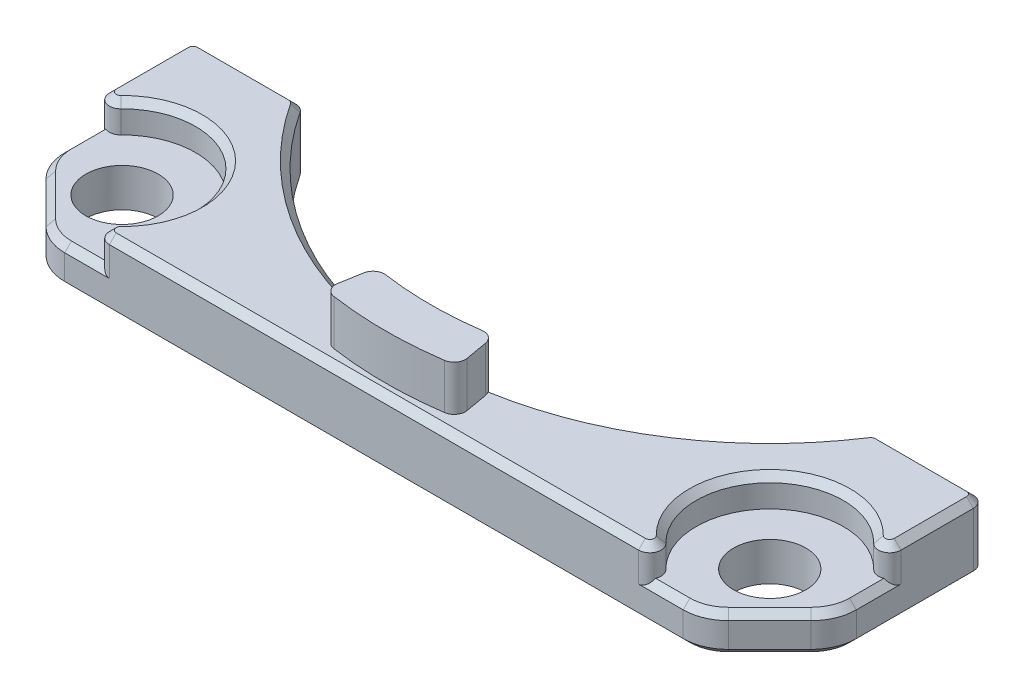
SolidWorks part; units mm, degrees
material "6061 合金"
ref_plane "前视基准面" through (0, 0, 0) normal (0, 0, 1) x (1, 0, 0)
ref_plane "上视基准面" through (0, 0, 0) normal (0, 1, 0) x (1, 0, 0)
ref_plane "右视基准面" through (0, 0, 0) normal (1, 0, 0) x (0, 0, -1)
other "Configuration Table"
sketch "草图1" plane through (0, 0, 0) normal (0, 1, 0) x (1, 0, 0)
  line L0 (-12.6886, -8) -> (-17.5, -8)
  line L1 (-17.5, 17.5) -> (17.5, 17.5) construction
  line L2 (-17.5, 17.5) -> (-17.5, -17.5) construction
  line L3 (-17.5, -17.5) -> (17.5, -17.5) construction
  line L4 (17.5, 17.5) -> (17.5, -17.5) construction
  line L5 (-17.5, 17.5) -> (17.5, -17.5) construction
  line L6 (-17.5, -17.5) -> (17.5, 17.5) construction
  line L7 (12.6886, -8) -> (17.5, -8)
  line L8 (-17.5, -8) -> (-17.5, -17.5)
  line L9 (-17.5, -17.5) -> (17.5, -17.5)
  line L10 (17.5, -17.5) -> (17.5, -8)
  arc A0 (-12.6886, -8) -> (12.6886, -8) centre (0, 0) ccw
  point P0 (0, 0)
  dimension "D3" = 30
  dimension "D1" = 35
  dimension "D2" = 35
  dimension "D4" = 8
extrude "凸台-拉伸1" add sketch "草图1" along normal blind 3
chamfer "倒角1" distance 3 angle 45 2 edges at (-17.5, 1.5, 17.5) (17.5, 1.5, 17.5)
sketch "草图2" plane through (0, 3, 0) normal (0, 1, 0) x (1, 0, 0)
  line L0 (0, 0) -> (14.3189, -14.3189) construction
  line L1 (0, 0) -> (0, -20.25) construction
  circle A0 centre (0, 0) radius 20.25 construction
  circle A1 centre (14.3189, -14.3189) radius 1.6
  circle A2 centre (-14.3189, -14.3189) radius 1.6
  dimension "D1" = 40.5
  dimension "D3" = 3.2
  dimension "D2" = 45
extrude "切除-拉伸1" cut sketch "草图2" against normal blind 3
sketch "草图3" plane through (0, 3, 0) normal (0, 1, 0) x (1, 0, 0)
  line L0 (-2.6047, -14.7721) -> (-2.952, -16.7417)
  line L1 (-14.5, -17.5) -> (14.5, -17.5) construction
  line L2 (0, 0) -> (0, -17.5) construction
  line L6 (2.6047, -14.7721) -> (2.952, -16.7417)
  arc A0 (-12.6886, -8) -> (12.6886, -8) centre (0, 0) ccw construction
  arc A1 (-2.6047, -14.7721) -> (2.6047, -14.7721) centre (0, 0) ccw
  arc A3 (-2.6047, -14.7721) -> (2.6047, -14.7721) centre (0, 0) ccw
  arc A4 (-2.952, -16.7417) -> (2.952, -16.7417) centre (0, 0) ccw
  arc M12 (12.6886, -8) -> (-12.6886, -8) centre (0, 0) cw
  dimension "D2" = 34
  dimension "D1" = 10
  dimension "D3" = 10
extrude "凸台-拉伸2" add sketch "草图3" along normal blind 2 contours L2 A3 L0 A4 | L2 A4 L6 M12 region at (-1.3945, 3, 15.9396) region at (1.3945, 3, 15.9396)
sketch "草图5" plane through (0, 3, 0) normal (0, 1, 0) x (1, 0, 0)
  circle A0 centre (-14.3189, -14.3189) radius 3.25
  circle A1 centre (14.3189, -14.3189) radius 3.25
  dimension "D1" = 6.5
  dimension "D2" = 6.5
extrude "切除-拉伸2" cut sketch "草图5" against normal blind 1.3
fillet "圆角1" radius 0.5 8 edges at (12.6886, 1.5, 8) (-12.6886, 1.5, 8) (-17.5, 1.5, 8) (17.5, 1.5, 8) (17.5, 2.35, 13.6532) (13.6532, 2.35, 17.5) (-13.6532, 2.35, 17.5) (-17.5, 2.35, 13.6532)
fillet "圆角5" radius 0.5 4 edges at (-2.6047, 4, 14.7721) (2.6047, 4, 14.7721) (2.952, 4, 16.7417) (-2.952, 4, 16.7417)
fillet "圆角4" radius 2 4 edges at (17.5, 0.85, 14.5) (14.5, 0.85, 17.5) (-14.5, 0.85, 17.5) (-17.5, 0.85, 14.5)
chamfer "倒角2" distance 0.3 angle 45 33 edges at (-17.5, 3, 10.0985) (-17.1888, 3, 12.16) (-17.3536, 3, 8.1464) (-12.0208, 3, 12.0208) (-14.9807, 3, 8) (-12.16, 3, 17.1888) (-12.7239, 3, 8.0601) (-8.0479, 3, 12.6583) (12.16, 3, 17.1888) (12.0208, 3, 12.0208) (17.1888, 3, 12.16) (17.5, 3, 10.0985) (17.3536, 3, 8.1464) (14.9807, 3, 8) (12.7239, 3, 8.0601) (8.0479, 3, 12.6583) (17.3536, 0, 8.1464) (14.9807, 0, 8) (12.7239, 0, 8.0601) (0, 0, 15) (-12.7239, 0, 8.0601) (-14.9807, 0, 8) (-17.3536, 0, 8.1464) (-17.5, 0, 11.0858) (-17.3478, 0, 14.4369) (-16, 0, 16) (-14.4369, 0, 17.3478) (0, 0, 17.5) (14.4369, 0, 17.3478) (16, 0, 16) (17.3478, 0, 14.4369) (17.5, 0, 11.0858) (0, 3, 17.5)
chamfer "倒角3" distance 0.3 angle 45 10 edges at (17.5, 1.7, 12.6843) (17.3478, 1.7, 14.4369) (16, 1.7, 16) (14.4369, 1.7, 17.3478) (12.6843, 1.7, 17.5) (-12.6843, 1.7, 17.5) (-14.4369, 1.7, 17.3478) (-16, 1.7, 16) (-17.3478, 1.7, 14.4369) (-17.5, 1.7, 12.6843)
